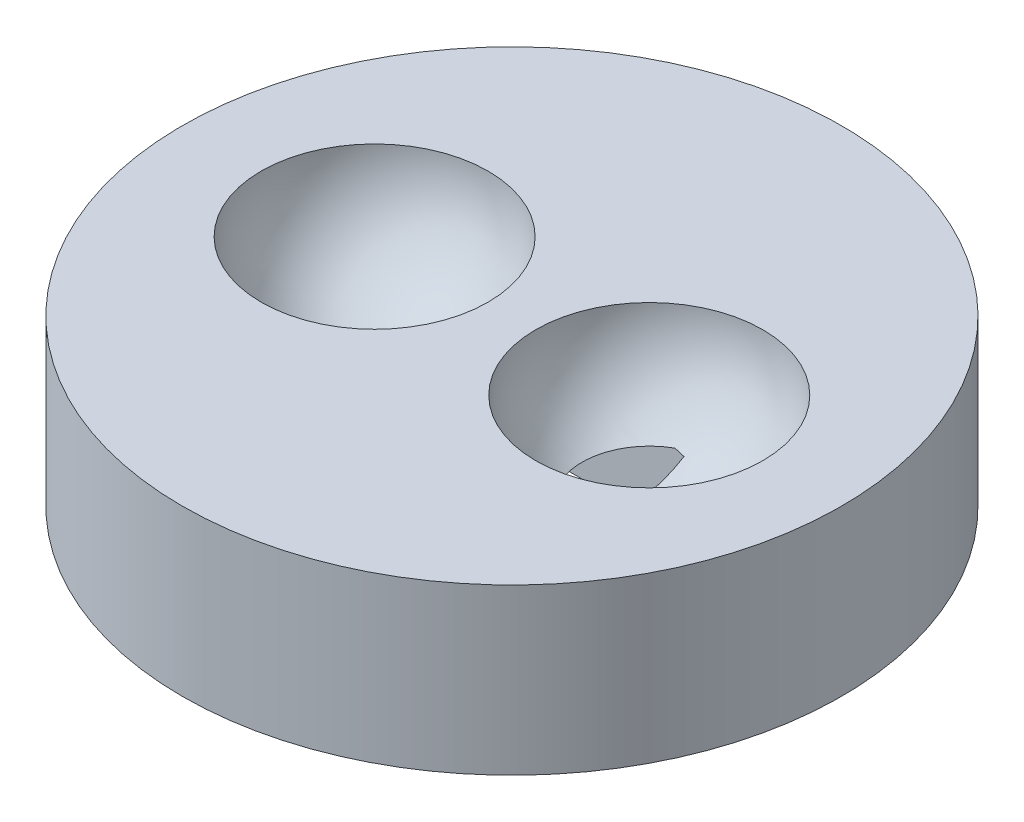
SolidWorks part; units mm, degrees
ref_plane "Спереди" through (0, 0, 0) normal (0, 0, 1) x (1, 0, 0)
ref_plane "Сверху" through (0, 0, 0) normal (0, 1, 0) x (1, 0, 0)
ref_plane "Справа" through (0, 0, 0) normal (1, 0, 0) x (0, 0, -1)
ref_axis "Axis1" through (0, 0, 0) along (0, 1, 0)
sketch "Sketch2" plane through (0, 0, 0) normal (0, 1, 0) x (1, 0, 0)
  circle A0 centre (0, 0) radius 9
  dimension "D1" = 18
extrude "Boss-Extrude1" add sketch "Sketch2" along normal blind 4.5
sketch "Sketch3" plane through (0, 0, 0) normal (0, -1, 0) x (1, 0, 0)
  line L1 (-3.1, -1.6) -> (3.1, -1.6)
  line L2 (-3.1, -1.6) -> (-3.1, 1.6)
  line L3 (-3.1, 1.6) -> (3.1, 1.6)
  line L4 (3.1, -1.6) -> (3.1, 1.6)
  line L5 (-3.1, -1.6) -> (3.1, 1.6) construction
  line L6 (-3.1, 1.6) -> (3.1, -1.6) construction
  point P0 (0, 0)
  dimension "D1" = 6.2
  dimension "D2" = 3.2
extrude "Cut-Extrude1" cut sketch "Sketch3" against normal blind 2
sketch "Sketch4" plane through (0, 4.5, 0) normal (0, 1, 0) x (1, 0, 0)
  line L0 (-3.75, 3.1) -> (-3.75, -3.1)
  arc A0 (-3.75, 3.1) -> (-3.75, -3.1) centre (-3.75, 0) ccw
  dimension "D1" = 6.2
  dimension "D2" = 3.75
revolve "Cut-Revolve1" cut sketch "Sketch4" angle 360 about L0
mirror "Mirror1" about plane through (0, 0, 0) normal (1, 0, 0) of "Cut-Revolve1"
